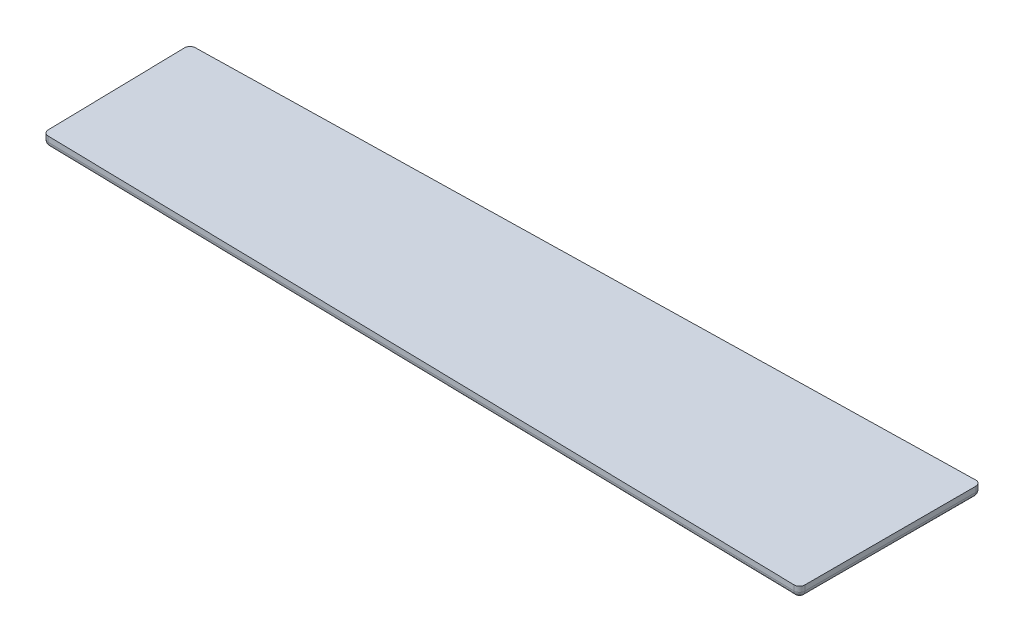
SolidWorks part; units mm, degrees
ref_plane "Front Plane" through (0, 0, 0) normal (0, 0, 1) x (1, 0, 0)
ref_plane "Top Plane" through (0, 0, 0) normal (0, 1, 0) x (1, 0, 0)
ref_plane "Right Plane" through (0, 0, 0) normal (1, 0, 0) x (0, 0, -1)
sketch "Sketch1" plane through (0, 0, 0) normal (0, 1, 0) x (1, 0, 0)
  line L0 (-92.0553, 17.78) -> (-91.3191, -17.7952)
  line L1 (-91.3191, -17.7952) -> (92.0553, -21.59)
  line L2 (92.0553, -21.59) -> (92.0553, 21.59)
  line L3 (92.0553, 21.59) -> (-92.0553, 17.78)
extrude "Boss-Extrude1" add sketch "Sketch1" along normal blind 2.54
fillet "Fillet1" radius 1.27 4 edges at (92.0553, 0, 0) (0, 0, -19.685) (-91.6872, 0, 0.0076) (0.3681, 0, 19.6926)
fillet "Fillet2" radius 1.27 8 edges at (-91.6757, 0.372, -17.4158) (-90.9546, 0.372, 17.4307) (91.6833, 0.372, 21.2102) (91.6833, 0.372, -21.2102) (-92.0553, 1.905, -17.78) (-91.3191, 1.905, 17.7952) (92.0553, 1.905, 21.59) (92.0553, 1.905, -21.59)
